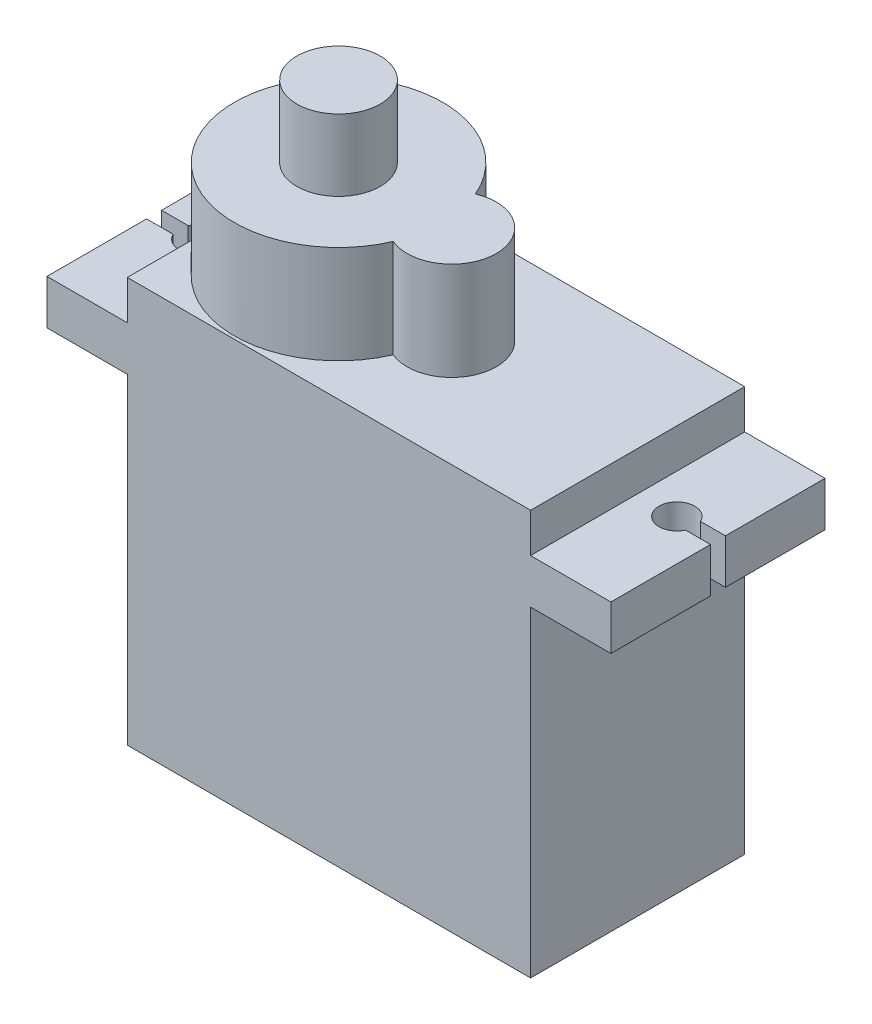
SolidWorks part; units mm, degrees
ref_plane "Front Plane" through (0, 0, 0) normal (0, 0, 1) x (1, 0, 0)
ref_plane "Top Plane" through (0, 0, 0) normal (0, 1, 0) x (1, 0, 0)
ref_plane "Right Plane" through (0, 0, 0) normal (1, 0, 0) x (0, 0, -1)
sketch "Sketch1" plane through (0, 0, 0) normal (0, 1, 0) x (1, 0, 0)
  line L1 (-46.1955, 4.7431) -> (-23.5955, 4.7431)
  line L2 (-46.1955, 4.7431) -> (-46.1955, -7.2569)
  line L3 (-46.1955, -7.2569) -> (-23.5955, -7.2569)
  line L4 (-23.5955, 4.7431) -> (-23.5955, -7.2569)
  dimension "Servo_length" = 22.6
  dimension "Servo_width" = 12
extrude "Boss-Extrude1" add sketch "Sketch1" along normal blind 22.7
ref_plane "Plane1" through (-23.5955, 22.7, -4.7431) normal (0, -1, 0) x (1, 0, 0)
sketch "Sketch2" plane through (-23.5955, 22.7, -4.7431) normal (0, -1, 0) x (1, 0, 0)
ref_plane "Plane2" through (-46.1955, 22.7, -4.7431) normal (0, 0, 1) x (1, 0, 0)
sketch "Sketch3" plane through (-46.1955, 22.7, -4.7431) normal (0, 0, 1) x (1, 0, 0)
sketch "Sketch4" plane through (0, 22.7, 0) normal (0, 1, 0) x (-1, 0, 0)
  line L0 (46.1955, 1.2569) -> (40.3555, 1.2569)
  line L1 (46.1955, -4.7431) -> (46.1955, 7.2569) construction
  circle A0 centre (40.3555, 1.2569) radius 5.84
  dimension "Servo_boss_radius" = 5.84
extrude "Boss-Extrude6" add sketch "Sketch4" along normal blind 5.5 contours A0 region at (-34.6807, 22.7, 1.2569)
sketch "Sketch12" plane through (0, 28.2, 0) normal (0, 1, 0) x (-1, 0, 0)
  circle A0 centre (40.3555, 1.2569) radius 2.335
extrude "Boss-Extrude7" add sketch "Sketch12" along normal blind 4
sketch "Sketch13" plane through (0, 22.7, 0) normal (0, 1, 0) x (-1, 0, 0)
  line L0 (34.5155, 1.2569) -> (34.0155, 1.2569)
  circle A0 centre (40.3555, 1.2569) radius 5.84 construction
  circle A1 centre (34.0155, 1.2569) radius 2.5
  circle M2 centre (40.3555, 1.2569) radius 5.84
extrude "Boss-Extrude8" add sketch "Sketch13" along normal blind 5.5 contours A1 M2 region at (-33.3061, 22.7, 1.2569)
sketch "Sketch14" plane through (-23.5955, 0, 0) normal (1, 0, 0) x (0, 0, -1)
  line L0 (-7.2569, 22.7) -> (-7.2569, 20.5)
  line L1 (-7.2569, 22.7) -> (-7.2569, 0) construction
  line L2 (4.7431, 22.7) -> (4.7431, 0) construction
  line L3 (-7.2569, 20.5) -> (4.7431, 20.5)
  line L4 (-7.2569, 20.5) -> (-7.2569, 18)
  line L5 (-7.2569, 18) -> (4.7431, 18)
  line L6 (4.7431, 20.5) -> (4.7431, 18)
  line L7 (-7.2569, 0) -> (4.7431, 0) construction
  line L8 (-7.2569, 22.7) -> (4.7431, 22.7) construction
  line M2 (4.7431, 0) -> (4.7431, 22.7)
  line M4 (-7.2569, 22.7) -> (-7.2569, 0)
  dimension "D3" = 2.2
  dimension "boss_height" = 18
  dimension "boss_thickness" = 2.5
extrude "Boss-Extrude10" add sketch "Sketch14" along normal blind 4.5 contours L5 L3 M4 M2 region at (-23.5955, 19.25, 1.2569)
sketch "Sketch15" plane through (0, 20.5, 0) normal (0, 1, 0) x (-1, 0, 0)
  line L0 (19.0955, 7.2569) -> (19.0955, -4.7431) construction
  line L1 (19.0955, 1.2569) -> (20.5955, 1.2569)
  line L2 (19.0955, 1.6769) -> (19.0955, 0.8369)
  line L3 (19.0955, 0.8369) -> (20.5955, 0.8369)
  line L4 (50.6955, 1.2569) -> (48.3955, 1.2569)
  line L5 (20.5955, 1.6769) -> (20.5955, 0.8369)
  line L6 (19.0955, 1.6769) -> (20.5955, 1.6769)
  line L7 (19.0955, 1.2569) -> (21.3955, 1.2569)
  circle A0 centre (21.3955, 1.2569) radius 1
  circle A1 centre (48.3955, 1.2569) radius 1
  line M3 (19.0955, 7.2569) -> (19.0955, -4.7431)
extrude "Cut-Extrude3" cut sketch "Sketch15" along direction (0, 1, 0) on the side against the normal through all contours L3 A0 L6 L5 | L6 A0 L7 L5 | L7 A0 L3 L5 | A0 L6 L1 M3 | A0 L1 L3 M3 region at (-19.7609, 20.5, 1.4693) region at (-19.7609, 20.5, 1.0445) region at (-20.5084, 20.5, 1.448) region at (-20.5084, 20.5, 1.0657) region at (-21.4377, 20.5, 1.2569)
sketch "Sketch16" plane through (-46.1955, 0, 0) normal (-1, 0, 0) x (0, 0, 1)
  line L0 (7.2569, 24.5) -> (7.2569, 20.5)
  line L1 (7.2569, 22.7) -> (7.2569, 0) construction
  line L2 (7.2569, 20.5) -> (7.2569, 18)
  line L3 (7.2569, 20.5) -> (-4.7431, 20.5)
  line L4 (-4.7431, 22.7) -> (-4.7431, 0) construction
  line L5 (7.2569, 18) -> (-4.7431, 18)
  line L6 (-4.7431, 0) -> (7.2569, 0) construction
  line L7 (-4.7431, 22.7) -> (1.2569, 22.7) construction
  line M2 (7.2569, 0) -> (7.2569, 22.7)
  line M5 (-4.7431, 22.7) -> (-4.7431, 0)
  dimension "D3" = 2.2
  dimension "boss_height" = 18
  dimension "boss_thickness" = 2.5
extrude "Boss-Extrude11" add sketch "Sketch16" along normal blind 4.5 contours L5 L3 M2 M5 region at (-46.1955, 19.25, 1.2569)
sketch "Sketch17" plane through (0, 20.5, 0) normal (0, 1, 0) x (-1, 0, 0)
  line L0 (50.6955, 0.8369) -> (50.6955, 1.6769)
  line L1 (50.6955, 1.2569) -> (49.1955, 1.2569)
  line L2 (50.6955, 1.6769) -> (49.1955, 1.6769)
  line L3 (49.1955, 0.8369) -> (49.1955, 1.6769)
  line L4 (50.6955, 7.2569) -> (50.6955, -4.7431) construction
  line L5 (50.6955, 0.8369) -> (49.1955, 0.8369)
  line L6 (50.6955, 1.2569) -> (48.2955, 1.2569)
  circle A0 centre (48.2955, 1.2569) radius 1
  line M3 (50.6955, -4.7431) -> (50.6955, 7.2569)
extrude "Cut-Extrude4" cut sketch "Sketch17" along direction (0, -1, 0) on the side against the normal through all contours L3 A0 | A0 L3 L5 L1 M3 | L3 A0 L6 | L6 A0 L3 | A0 L1 L0 L2 L3 region at (-49.9802, 20.5, 1.0446) region at (-49.9802, 20.5, 1.4691) region at (-48.2777, 20.5, 1.2569) region at (-49.2358, 20.5, 1.0928) region at (-49.2358, 20.5, 1.4209)
